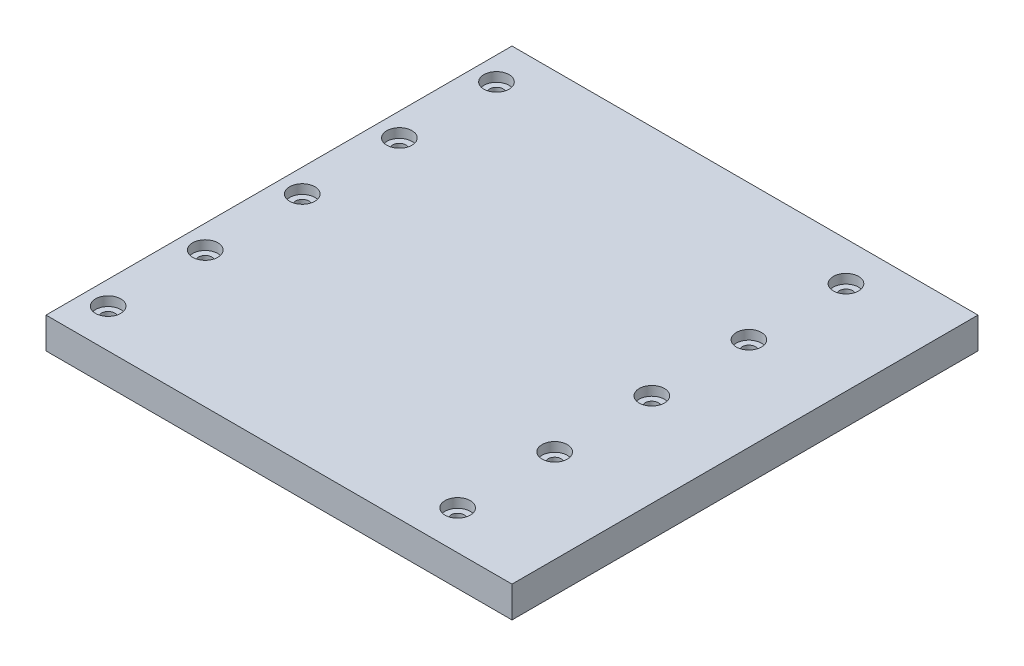
SolidWorks part; units mm, degrees
material "6061-T6 (SS)"
ref_plane "Front Plane" through (0, 0, 0) normal (0, 0, 1) x (1, 0, 0)
ref_plane "Top Plane" through (0, 0, 0) normal (0, 1, 0) x (1, 0, 0)
ref_plane "Right Plane" through (0, 0, 0) normal (1, 0, 0) x (0, 0, -1)
sketch "Sketch1" plane through (0, 0, 0) normal (0, 1, 0) x (1, 0, 0)
  line L1 (0, 0) -> (120, 0)
  line L2 (0, 0) -> (0, 120)
  line L3 (0, 120) -> (120, 120)
  line L4 (120, 0) -> (120, 120)
  dimension "D1" = 120
extrude "Boss-Extrude1" add sketch "Sketch1" along normal blind 8
sketch "Sketch2" plane through (0, 8, 0) normal (0, 1, 0) x (1, 0, 0)
  line L0 (0, 120) -> (6, 120)
  line L1 (120, 120) -> (0, 120) construction
  line L2 (6, 120) -> (6, 0)
  line L3 (0, 0) -> (120, 0) construction
  line L4 (0, 120) -> (0, 0) construction
  line L5 (96, 120) -> (96, 0) construction
  line L7 (120, 0) -> (120, 120) construction
  point P11 (6, 110)
  point P18 (6, 85)
  point P19 (6, 60)
  point P20 (6, 35)
  point P21 (6, 10)
  point P32 (96, 60)
  point P41 (96, 35)
  point P42 (96, 10)
  point P43 (96, 60)
  point P44 (96, 35)
  point P45 (96, 85)
  point P46 (96, 60)
  point P47 (96, 85)
  point P48 (96, 110)
  dimension "D1" = 5
  dimension "D2" = 10
  dimension "D3" = 6
  dimension "D4" = 24
  dimension "D5" = 3
  dimension "D6" = 3
hole_wizard "CBORE for M3 Hex Socket Thin Head Cap Screw1" positions "Sketch2" profile "Sketch3" counterbore size "M3" standard "DIN" end condition through all
sketch "Sketch3" plane through (96, 8, -110) normal (1, 0, 0) x (0, 0, 1)
  line L0 (0, 0) -> (0, 8)
  line L1 (0, 8) -> (1.7, 8)
  line L3 (1.7, 8) -> (1.7, 2.4)
  line L4 (1.7, 2.4) -> (3.25, 2.4)
  line L5 (3.25, 2.4) -> (3.25, 0)
  line L7 (3.25, 0) -> (0, 0)
  line L11 (0, -6.35) -> (0, 107.95) construction
  dimension "Thru Hole Dia." = 3.4
  dimension "Thru Hole Depth" = 8
  dimension "C'Bore Dia." = 6.5
  dimension "C'Bore Depth" = 2.4
